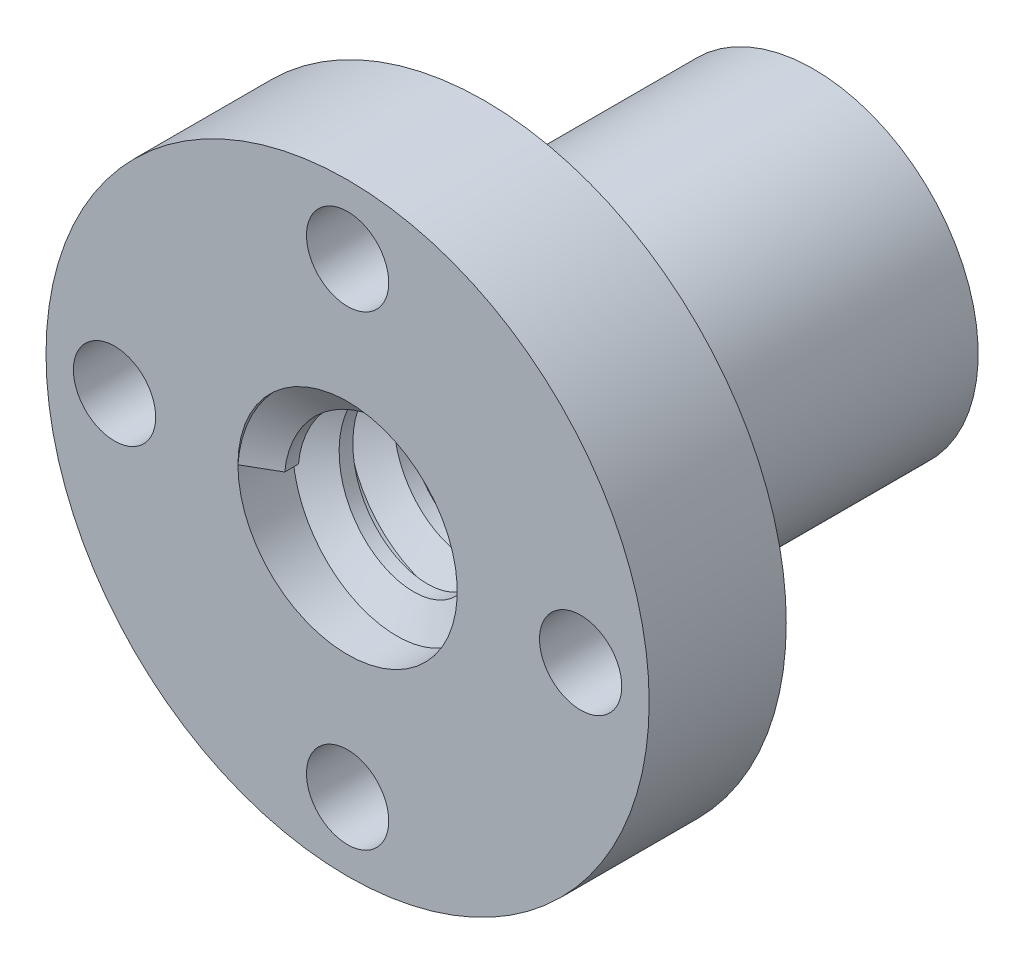
SolidWorks part; units mm, degrees
ref_plane "Front Plane" through (0, 0, 0) normal (0, 0, 1) x (1, 0, 0)
ref_plane "Top Plane" through (0, 0, 0) normal (0, 1, 0) x (1, 0, 0)
ref_plane "Right Plane" through (0, 0, 0) normal (1, 0, 0) x (0, 0, -1)
sketch "Sketch2" plane through (0, 0, 0) normal (0, 0, 1) x (1, 0, 0)
  circle A0 centre (0, 0) radius 11
  dimension "D2" = 22
  dimension "D3" = 0
  dimension "D4" = 0
extrude "Boss-Extrude1" add sketch "Sketch2" along normal blind 5
sketch "Sketch4" plane through (0, 0, 0) normal (0, 0, -1) x (-1, 0, 0)
  circle A0 centre (0, 0) radius 6
  dimension "D1" = 12
extrude "Boss-Extrude2" add sketch "Sketch4" along normal blind 10
sketch "Sketch5" plane through (0, 0, 5) normal (0, 0, 1) x (1, 0, 0)
  circle A0 centre (0, 0) radius 4
  dimension "D1" = 8
extrude "Cut-Extrude1" cut sketch "Sketch5" against normal through all both and the other way through all
thread "Thread1" pitch 2 method extrude profile "Thread Profile1" start angle 0, offset 0, length 0, pitch 2, diameter 8
ref_plane "Plane1" through (-4, 0, 5) normal (0, -1, 0) x (-1, 0, 0)
sketch "Thread Profile1" plane through (-4, 0, 5) normal (0, -1, 0) x (-1, 0, 0)
  line L0 (0, 0) -> (0, 2) construction
  line L11 (0, 0) -> (0, 1.75)
  line L12 (0, 1.75) -> (-1.0825, 1.125)
  line L13 (-1.0825, 1.125) -> (-1.0825, 0.625)
  line L15 (-1.0825, 0.625) -> (0, 0)
  line L17 (-1.0825, 0.875) -> (0, 0.875) construction
  point P2 (0, 0)
  dimension "Pitch" = 2
  dimension "Profile_Angle" = 60
  dimension "Profile_Land" = 0.5
  dimension "Profile_Height" = 1.0825
sketch "Sketch10" plane through (0, 0, -10) normal (0, 0, -1) x (-1, 0, 0)
  circle A0 centre (0, 0) radius 6
  circle A1 centre (0, 0) radius 4
  dimension "D1" = 12
  dimension "D2" = 8
extrude "Boss-Extrude3" add sketch "Sketch10" along normal blind 2
sketch "Sketch16" plane through (0, 0, 0) normal (0, 0, -1) x (-1, 0, 0)
  circle A0 centre (8.5, 0) radius 1.5
  dimension "D1" = 3
  dimension "D2" = 0
  dimension "D3" = 8.5
extrude "Cut-Extrude2" cut sketch "Sketch16" against normal up to next
pattern_circular "CirPattern1" count 4 over 360 about axis through (0, 0, -10) along (0, 0, 1) of "Cut-Extrude2"
